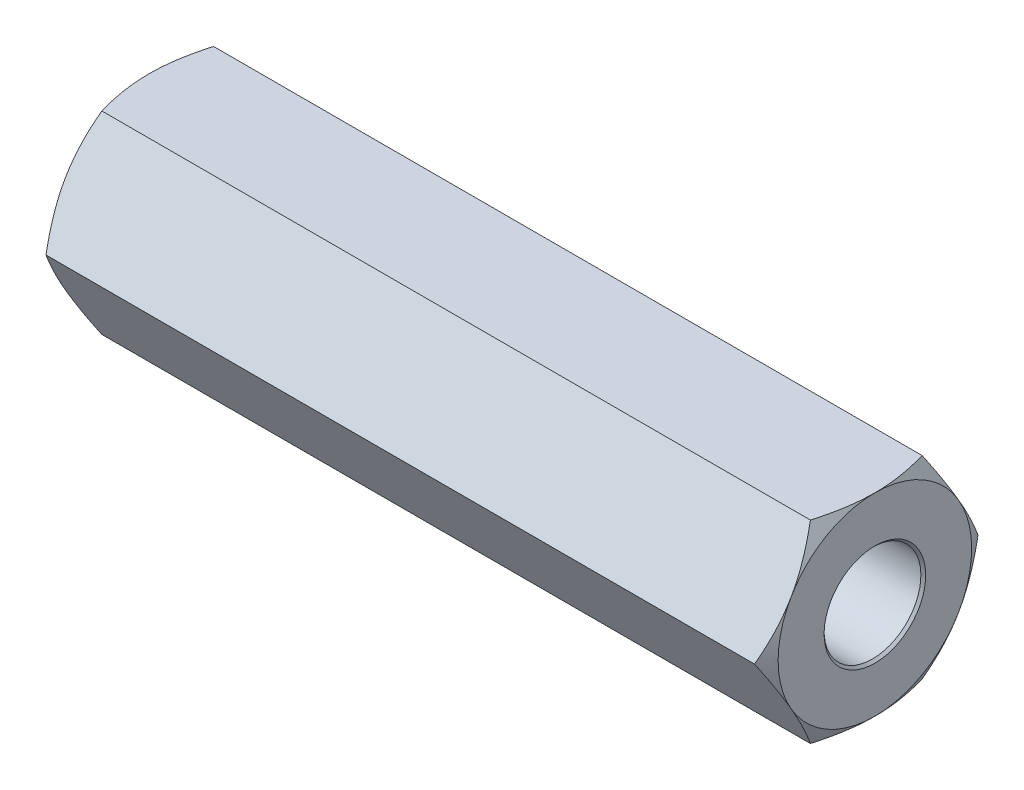
SolidWorks part; units mm, degrees
material "6061-T6 (SS)"
ref_plane "Front Plane" through (0, 0, 0) normal (0, 0, 1) x (1, 0, 0)
ref_plane "Top Plane" through (0, 0, 0) normal (0, 1, 0) x (1, 0, 0)
ref_plane "Right Plane" through (0, 0, 0) normal (1, 0, 0) x (0, 0, -1)
sketch "Sketch1" plane through (0, 0, 0) normal (0, 0, 1) x (1, 0, 0)
  line L0 (0, 0) -> (30, 0) construction
  line L1 (0, 4) -> (0, -4) construction
  line L2 (0, 2) -> (11.1, 2) construction
  line L3 (0, 2) -> (-0.7, 2) construction
  line L4 (0, 4) -> (30, 4) construction
  point P6 (0, 0)
  dimension "Hex" = 8
  dimension "Pitch" = 0.7
  dimension "Thread Length" = 11.1
  dimension "Thread OD" = 4
  dimension "Length" = 30
sketch "Sketch2" plane through (0, 0, 0) normal (1, 0, 0) x (0, 0, -1)
  line L0 (0, 0) -> (-1.4142, -1.4142) construction
  line L1 (2.3094, 4) -> (-2.3094, 4)
  line L2 (-2.3094, 4) -> (-4.6188, 0)
  line L3 (-4.6188, 0) -> (-2.3094, -4)
  line L4 (-2.3094, -4) -> (2.3094, -4)
  line L5 (2.3094, -4) -> (4.6188, 0)
  line L6 (4.6188, 0) -> (2.3094, 4)
  circle A0 centre (0, 0) radius 4 construction
  circle A1 centre (0, 0) radius 2 construction
  dimension "D1" = 45
extrude "Boss-Extrude1" add sketch "Sketch2" along normal up to vertex (30 mm away) up to point (30, 0, 0)
sketch "Sketch3" plane through (0, 0, 0) normal (0, 0, 1) x (1, 0, 0)
  line L0 (0, 2.1) -> (0.1, 2)
  line L1 (0, 0) -> (11.1, 0)
  line L2 (0, 0) -> (0, 2.1)
  line L3 (0.1, 2) -> (11.1, 2)
  line L4 (11.1, 0) -> (11.1, 2)
  line L5 (30, 0) -> (18.9, 0)
  line L8 (18.9, 0) -> (18.9, 2)
  line L9 (0, 4) -> (0, -4) construction
  line L13 (0, 0) -> (30, 0) construction
  line L14 (18.9, 2) -> (29.9, 2)
  line L15 (29.9, 2) -> (30, 2.1)
  line L16 (30, 4) -> (30, 0) construction
  line L17 (30, 2.1) -> (30, 0)
  dimension "D1" = 4.2
  dimension "D2" = 45
revolve "Cut-Revolve1" cut sketch "Sketch3" angle 360 about L13
sketch "Sketch4" plane through (0, 0, 0) normal (-1, 0, 0) x (0, 0, 1)
  circle A0 centre (0, 0) radius 4
  circle A1 centre (0, 0) radius 4 construction
extrude "Cut-Extrude1" cut sketch "Sketch4" against normal through all draft 60 flip side to cut
sketch "Sketch5" plane through (30, 0, 0) normal (1, 0, 0) x (0, 0, -1)
  circle A0 centre (0, 0) radius 4
  circle A1 centre (0, 0) radius 4 construction
extrude "Cut-Extrude2" cut sketch "Sketch5" against normal through all draft 60 flip side to cut
ref_axis "Center Axis 1" through (0, 0, 0) along (1, 0, 0)
sketch "Sketch6" [suppressed] plane through (0, 0, 0) normal (0, 0, 1) x (1, 0, 0)
  line L0 (-0.599, 2) -> (-0.2995, 1.4813) construction
  line L1 (-0.2995, 1.4813) -> (0, 2) construction
  line L2 (0, 2) -> (-0.599, 2) construction
  line L3 (0, 2) -> (-0.7, 2) construction
  line L5 (-0.599, 2) -> (-0.6495, 2.0875) construction
  line L6 (-0.6495, 2.0875) -> (0.0505, 2.0875) construction
  line L7 (0.0505, 2.0875) -> (0, 2) construction
  line L8 (-0.3432, 1.5571) -> (-0.2557, 1.5571) construction
  line L9 (-0.2995, 2) -> (-0.2995, 2.0875) construction
  line L10 (-0.6242, 2.0438) -> (0.0253, 2.0438)
  line L11 (0.0253, 2.0438) -> (-0.2557, 1.5571)
  line L12 (-0.2557, 1.5571) -> (-0.3432, 1.5571)
  line L13 (-0.3432, 1.5571) -> (-0.6242, 2.0438)
  dimension "D1" = 0.0875
sketch "Sketch7" [suppressed] plane through (0, 0, 0) normal (-1, 0, 0) x (0, 0, 1)
  line L0 (0, 4) -> (0, -4) construction
  circle A0 centre (0, 0) radius 2
curve "Helix/Spiral1" [suppressed] pitch 0.7 height 11.8 turns 16.8571
sweep "Sweep1" [suppressed] add profiles "Sketch6" path "Helix/Spiral1"
pattern_linear "LPattern1" [suppressed] count 2 spacing 18.9 along (1, 0, 0)
combine bodies "Combine1" [suppressed] operation type add bodies to combine 107 108 109
sketch "Sketch8" [suppressed] plane through (0, 0, 0) normal (-1, 0, 0) x (0, 0, 1)
  circle A0 centre (0, 0) radius 2.1
extrude "Cut-Extrude3" [suppressed] cut sketch "Sketch8" against normal through all draft 45 and the other way through all draft 45
sketch "Sketch9" [suppressed] plane through (30, 0, 0) normal (1, 0, 0) x (0, 0, -1)
  circle A0 centre (0, 0) radius 2.1
  circle A1 centre (0, 0) radius 2.1 construction
extrude "Cut-Extrude4" [suppressed] cut sketch "Sketch9" against normal through all draft 45 and the other way through all draft 45
equation "\"D1@Sketch3\"=\"Thread OD@Sketch1\"*1.05"
equation "\"D1@Sketch6\"=\"Pitch@Sketch1\"/8"
equation "\"D4@Helix/Spiral1\"=\"Pitch@Sketch1\""
equation "\"D3@Helix/Spiral1\"=\"Pitch@Sketch1\"+\"Thread Length@Sketch1\""
equation "\"D3@LPattern1\"=\"Length@Sketch1\"-\"Thread Length@Sketch1\""
